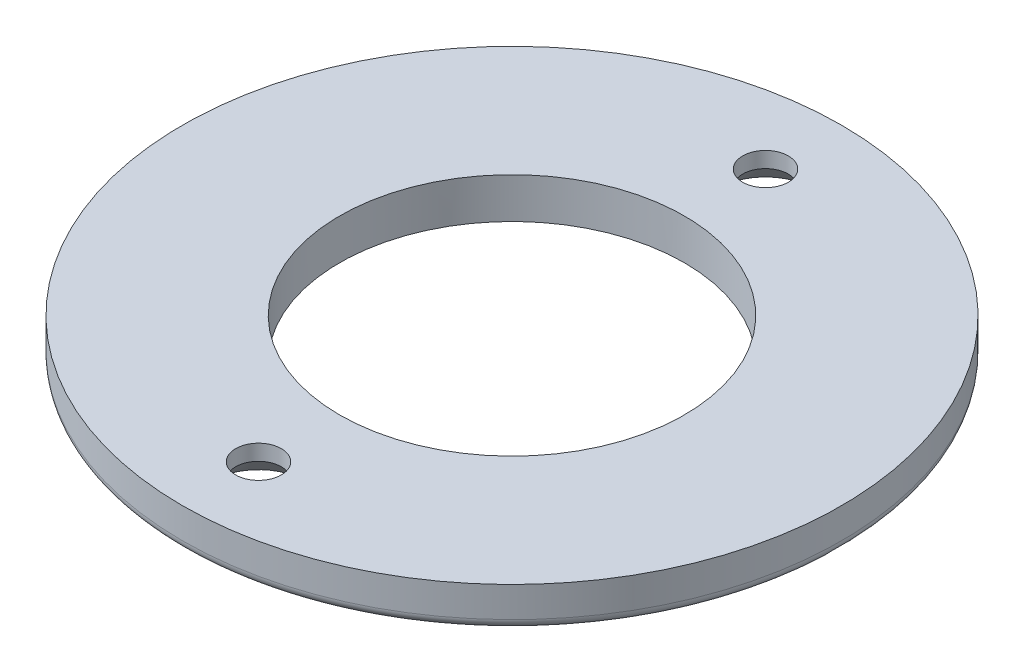
SolidWorks part; units mm, degrees
note: '?' marks a value the reader was unsure of.
ref_plane "Front Plane" through (0, 0, 0) normal (0, 0, 1) x (1, 0, 0)
ref_plane "Top Plane" through (0, 0, 0) normal (0, 1, 0) x (1, 0, 0)
ref_plane "Right Plane" through (0, 0, 0) normal (1, 0, 0) x (0, 0, -1)
ref_axis "X" through (88.99, 0, 0) along (-1, 0, 0)?
ref_axis "Y" through (0, 55, 0) along (0, -1, 0)?
ref_axis "Z" through (0, 0, -88.99) along (0, 0, 1)?
sketch "Sketch1" plane through (0, 0, 0) normal (0, 0, 1) x (1, 0, 0)
  line L0 (0, 0) -> (0, -21.8723) construction
  line L4 (-32.5, 0) -> (-32.5, 4)
  line L5 (-32.5, 4) -> (-17, 4)
  line L6 (-17, 4) -> (-17, 2)
  line L7 (-17, 2) -> (0, 2)
  line L8 (0, 2) -> (0, 0)
  line L9 (0, 0) -> (-32.5, 0)
  dimension "D1" = 65
  dimension "D2" = 34
  dimension "D3" = 4
  dimension "D4" = 2
revolve "Revolve1" add sketch "Sketch1" angle 360 about L0
hole_wizard "CSK SLOT for M4 Countersunk Flat Head Screw1" positions "Sketch2" profile "Sketch3" size "M4" standard "DIN" slot yes end condition up to next
sketch "Sketch2" plane through (0, 0, 0) normal (0, 1, 0) x (1, 0, 0)
  circle A0 centre (0, 0) radius 25
  point P5 (0, 25)
  point P9 (0, -25)
  dimension "D1" = 50
sketch "Sketch3" plane through (0, 0, 25) normal (1, 0, 0) x (0, 0, -1)
  line L0 (0, 0) -> (0, 4)
  line L1 (0, 4) -> (2.25, 4)
  line L2 (2.25, 4) -> (2.25, 2.45)
  line L3 (2.25, 2.45) -> (4.7, 0)
  line L5 (4.7, 0) -> (0, 0)
  line L6 (-2.25, 2.45) -> (-4.7, 0) construction
  line L11 (0, -6.35) -> (0, 107.95) construction
  dimension "Thru Hole Dia." = 4.5
  dimension "Thru Hole Depth" = 4
  dimension "Near C'Sink Dia." = 9.4
  dimension "Near C'Sink Angle" = 90
sketch "Sketch4" [suppressed] plane through (0, 2, 0) normal (0, 1, 0) x (1, 0, 0)
  circle A0 centre (0, 0) radius 17
  dimension "D1" = 34
extrude "Cut-Extrude1" [suppressed] cut sketch "Sketch4" against normal through all
fillet "Fillet1" radius 1 2 edges at (0, 2, 17) (0, 0, 32.5)
sketch "Sketch5" plane through (0, 4, 0) normal (0, 1, 0) x (1, 0, 0)
  circle A0 centre (0, 0) radius 17
extrude "Cut-Extrude2" cut sketch "Sketch5" against normal blind 10
